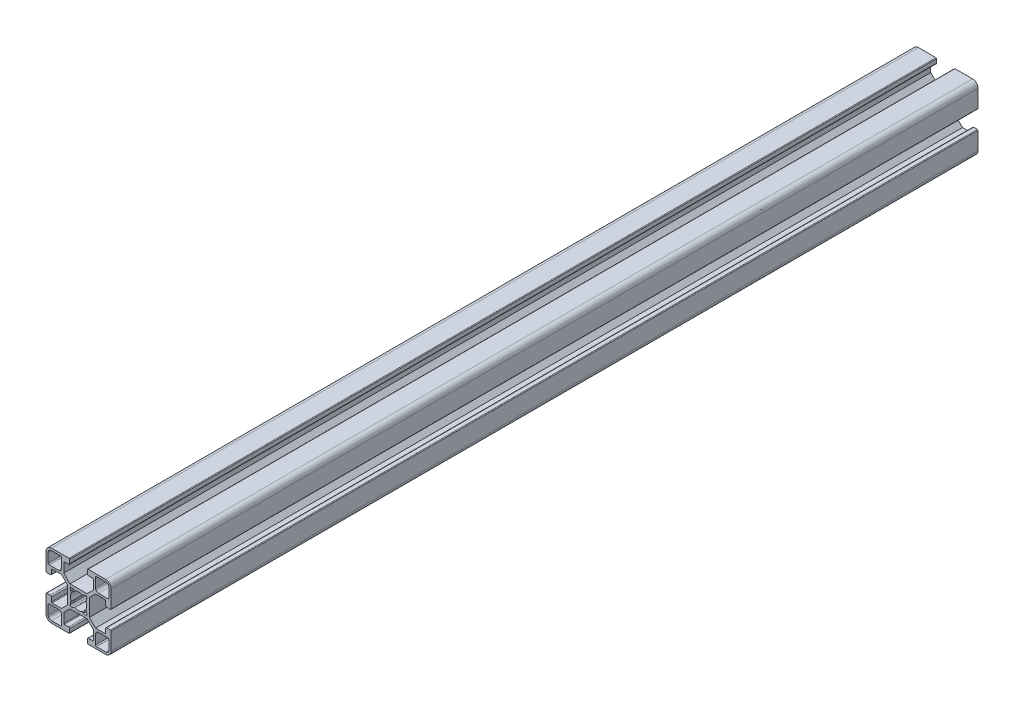
SolidWorks part; units mm, degrees
ref_plane "Front Plane" through (0, 0, 0) normal (0, 0, 1) x (1, 0, 0)
ref_plane "Top Plane" through (0, 0, 0) normal (0, 1, 0) x (1, 0, 0)
ref_plane "Right Plane" through (0, 0, 0) normal (1, 0, 0) x (0, 0, -1)
sketch "Sketch1" plane through (0, 0, 0) normal (0, 0, 1) x (1, 0, 0)
  line L0 (18.8789, 11.7141) -> (18.6573, 12.7569)
  line L1 (11.3427, 17.2431) -> (11.1211, 18.2859)
  line L2 (12.9949, 18.4193) -> (12.7569, 18.6573)
  line L3 (21.8, 7.1394) -> (18.9393, 10)
  line L4 (22.8607, 8.2) -> (20, 11.0607)
  line L5 (11.5807, 17.0051) -> (11.3427, 17.2431)
  line L6 (17.2431, 11.3427) -> (17.0051, 11.5806)
  line L7 (10, 18.9393) -> (7.1393, 21.8)
  line L8 (11.0607, 20) -> (8.2, 22.8606)
  line L9 (18.6573, 12.7569) -> (18.4193, 12.9948)
  line L10 (18.2859, 11.1211) -> (17.2431, 11.3427)
  line L11 (12.7569, 18.6573) -> (11.7141, 18.8789)
  line L12 (2.5, 0) -> (10.6, 0)
  line L13 (19.4, 0) -> (27.5, 0)
  line L14 (23.3, 1) -> (27.5, 1)
  line L15 (2.5, 1) -> (6.7, 1)
  line L16 (8.5, 2.5) -> (10.4, 2.5)
  line L17 (19.6, 2.5) -> (21.5, 2.5)
  line L18 (24.3, 7.2) -> (28.5, 7.2)
  line L19 (1.5, 7.2) -> (5.7, 7.2)
  line L20 (2.8, 8.2) -> (7.1393, 8.2)
  line L21 (22.8607, 8.2) -> (27.2, 8.2)
  line L22 (11.0607, 10) -> (18.9393, 10)
  line L23 (0.3, 10.9) -> (2, 10.9)
  line L24 (28, 10.9) -> (29.7, 10.9)
  line L25 (0.3, 19.1) -> (2, 19.1)
  line L26 (28, 19.1) -> (29.7, 19.1)
  line L27 (11.0607, 20) -> (18.9393, 20)
  line L28 (2.8, 21.8) -> (7.1393, 21.8)
  line L29 (22.8607, 21.8) -> (27.2, 21.8)
  line L30 (1.5, 22.8) -> (5.7, 22.8)
  line L31 (24.3, 22.8) -> (28.5, 22.8)
  line L32 (19.6, 27.5) -> (21.5, 27.5)
  line L33 (8.5, 27.5) -> (10.4, 27.5)
  line L34 (2.5, 29) -> (6.7, 29)
  line L35 (23.3, 29) -> (27.5, 29)
  line L36 (19.4, 30) -> (27.5, 30)
  line L37 (2.5, 30) -> (10.6, 30)
  line L38 (11.7141, 11.1211) -> (12.7569, 11.3427)
  line L39 (17.2431, 18.6573) -> (18.2859, 18.8789)
  line L40 (18.4194, 17.0051) -> (18.6573, 17.2431)
  line L41 (8.2, 7.1393) -> (11.0607, 10)
  line L42 (7.1393, 8.2) -> (10, 11.0607)
  line L43 (12.7569, 11.3427) -> (12.9949, 11.5806)
  line L44 (11.3427, 12.7569) -> (11.5807, 12.9949)
  line L45 (20, 18.9393) -> (22.8607, 21.8)
  line L46 (18.9393, 20) -> (21.8, 22.8606)
  line L47 (17.0051, 18.4193) -> (17.2431, 18.6573)
  line L48 (11.1211, 11.7141) -> (11.3427, 12.7569)
  line L49 (18.6573, 17.2431) -> (18.8789, 18.2859)
  line L50 (0, 19.4) -> (0, 27.5)
  line L51 (0, 2.5) -> (0, 10.6)
  line L52 (1, 23.3) -> (1, 27.5)
  line L53 (1, 2.5) -> (1, 6.7)
  line L54 (2.5, 8.5) -> (2.5, 10.4)
  line L55 (2.5, 19.6) -> (2.5, 21.5)
  line L56 (7.2, 24.3) -> (7.2, 28.5)
  line L57 (7.2, 1.5) -> (7.2, 5.7)
  line L58 (8.2, 2.8) -> (8.2, 7.1393)
  line L59 (8.2, 22.8606) -> (8.2, 27.2)
  line L60 (10, 11.0607) -> (10, 18.9393)
  line L61 (10.9, 0.3) -> (10.9, 2)
  line L62 (10.9, 28) -> (10.9, 29.7)
  line L63 (19.1, 0.3) -> (19.1, 2)
  line L64 (19.1, 28) -> (19.1, 29.7)
  line L65 (20, 11.0607) -> (20, 18.9393)
  line L66 (21.8, 2.8) -> (21.8, 7.1394)
  line L67 (21.8, 22.8606) -> (21.8, 27.2)
  line L68 (22.8, 24.3) -> (22.8, 28.5)
  line L69 (22.8, 1.5) -> (22.8, 5.7)
  line L70 (27.5, 8.5) -> (27.5, 10.4)
  line L71 (27.5, 19.6) -> (27.5, 21.5)
  line L72 (29, 23.3) -> (29, 27.5)
  line L73 (29, 2.5) -> (29, 6.7)
  line L74 (30, 2.5) -> (30, 10.6)
  line L75 (30, 19.4) -> (30, 27.5)
  line L76 (15, 36.6844) -> (15, -6.6844) construction
  line L77 (-9.3806, 15) -> (40.1263, 15) construction
  arc A0 (0.3, 10.9) -> (0, 10.6) centre (0.3, 10.6) ccw
  arc A1 (0, 19.4) -> (0.3, 19.1) centre (0.3, 19.4) ccw
  arc A2 (1.5, 7.2) -> (1, 6.7) centre (1.5, 6.7) ccw
  arc A3 (1, 23.3) -> (1.5, 22.8) centre (1.5, 23.3) ccw
  arc A4 (2.5, 10.4) -> (2, 10.9) centre (2, 10.4) ccw
  arc A5 (2, 19.1) -> (2.5, 19.6) centre (2, 19.6) ccw
  arc A6 (1, 2.5) -> (2.5, 1) centre (2.5, 2.5) ccw
  arc A7 (0, 2.5) -> (2.5, 0) centre (2.5, 2.5) ccw
  arc A8 (2.5, 29) -> (1, 27.5) centre (2.5, 27.5) ccw
  arc A9 (2.5, 30) -> (0, 27.5) centre (2.5, 27.5) ccw
  arc A10 (2.5, 8.5) -> (2.8, 8.2) centre (2.8, 8.5) ccw
  arc A11 (2.8, 21.8) -> (2.5, 21.5) centre (2.8, 21.5) ccw
  arc A12 (7.2, 5.7) -> (5.7, 7.2) centre (5.7, 5.7) ccw
  arc A13 (5.7, 22.8) -> (7.2, 24.3) centre (5.7, 24.3) ccw
  arc A14 (6.7, 1) -> (7.2, 1.5) centre (6.7, 1.5) ccw
  arc A15 (7.2, 28.5) -> (6.7, 29) centre (6.7, 28.5) ccw
  arc A16 (8.2, 2.8) -> (8.5, 2.5) centre (8.5, 2.8) ccw
  arc A17 (8.5, 27.5) -> (8.2, 27.2) centre (8.5, 27.2) ccw
  arc A18 (10.9, 2) -> (10.4, 2.5) centre (10.4, 2) ccw
  arc A19 (10.4, 27.5) -> (10.9, 28) centre (10.4, 28) ccw
  arc A20 (10.6, 0) -> (10.9, 0.3) centre (10.6, 0.3) ccw
  arc A21 (10.9, 29.7) -> (10.6, 30) centre (10.6, 29.7) ccw
  arc A22 (11.5807, 12.9949) -> (11.6375, 13.3398) centre (11.3685, 13.207) ccw
  arc A23 (11.6375, 16.6602) -> (11.5807, 17.0051) centre (11.3685, 16.793) ccw
  arc A24 (11.1211, 11.7141) -> (11.7141, 11.1211) centre (11.6102, 11.6102) ccw
  arc A25 (11.7141, 18.8789) -> (11.1211, 18.2859) centre (11.6102, 18.3898) ccw
  arc A26 (13.3398, 11.6375) -> (12.9949, 11.5806) centre (13.207, 11.3685) ccw
  arc A27 (12.9949, 18.4193) -> (13.3398, 18.3625) centre (13.207, 18.6315) ccw
  arc A28 (11.6375, 16.6602) -> (11.6375, 13.3398) centre (15, 15) ccw
  arc A29 (16.6602, 18.3625) -> (13.3398, 18.3625) centre (15, 15) ccw
  arc A30 (18.3625, 13.3398) -> (18.3625, 16.6602) centre (15, 15) ccw
  arc A31 (13.3398, 11.6375) -> (16.6602, 11.6375) centre (15, 15) ccw
  arc A32 (17.0051, 11.5806) -> (16.6602, 11.6375) centre (16.793, 11.3685) ccw
  arc A33 (16.6602, 18.3625) -> (17.0051, 18.4193) centre (16.793, 18.6315) ccw
  arc A34 (18.2859, 11.1211) -> (18.8789, 11.7141) centre (18.3898, 11.6102) ccw
  arc A35 (18.8789, 18.2859) -> (18.2859, 18.8789) centre (18.3898, 18.3898) ccw
  arc A36 (18.3625, 13.3398) -> (18.4193, 12.9948) centre (18.6315, 13.207) ccw
  arc A37 (18.4194, 17.0051) -> (18.3625, 16.6602) centre (18.6315, 16.793) ccw
  arc A38 (19.1, 0.3) -> (19.4, 0) centre (19.4, 0.3) ccw
  arc A39 (19.4, 30) -> (19.1, 29.7) centre (19.4, 29.7) ccw
  arc A40 (19.6, 2.5) -> (19.1, 2) centre (19.6, 2) ccw
  arc A41 (19.1, 28) -> (19.6, 27.5) centre (19.6, 28) ccw
  arc A42 (21.5, 2.5) -> (21.8, 2.8) centre (21.5, 2.8) ccw
  arc A43 (21.8, 27.2) -> (21.5, 27.5) centre (21.5, 27.2) ccw
  arc A44 (22.8, 1.5) -> (23.3, 1) centre (23.3, 1.5) ccw
  arc A45 (23.3, 29) -> (22.8, 28.5) centre (23.3, 28.5) ccw
  arc A46 (24.3, 7.2) -> (22.8, 5.7) centre (24.3, 5.7) ccw
  arc A47 (22.8, 24.3) -> (24.3, 22.8) centre (24.3, 24.3) ccw
  arc A48 (27.2, 8.2) -> (27.5, 8.5) centre (27.2, 8.5) ccw
  arc A49 (27.5, 21.5) -> (27.2, 21.8) centre (27.2, 21.5) ccw
  arc A50 (27.5, 1) -> (29, 2.5) centre (27.5, 2.5) ccw
  arc A51 (27.5, 0) -> (30, 2.5) centre (27.5, 2.5) ccw
  arc A52 (29, 27.5) -> (27.5, 29) centre (27.5, 27.5) ccw
  arc A53 (30, 27.5) -> (27.5, 30) centre (27.5, 27.5) ccw
  arc A54 (28, 10.9) -> (27.5, 10.4) centre (28, 10.4) ccw
  arc A55 (27.5, 19.6) -> (28, 19.1) centre (28, 19.6) ccw
  arc A56 (29, 6.7) -> (28.5, 7.2) centre (28.5, 6.7) ccw
  arc A57 (28.5, 22.8) -> (29, 23.3) centre (28.5, 23.3) ccw
  arc A58 (30, 10.6) -> (29.7, 10.9) centre (29.7, 10.6) ccw
  arc A59 (29.7, 19.1) -> (30, 19.4) centre (29.7, 19.4) ccw
extrude "Boss-Extrude1" add sketch "Sketch1" along normal mid plane 400
equation "\"LENGTH\"=500"
